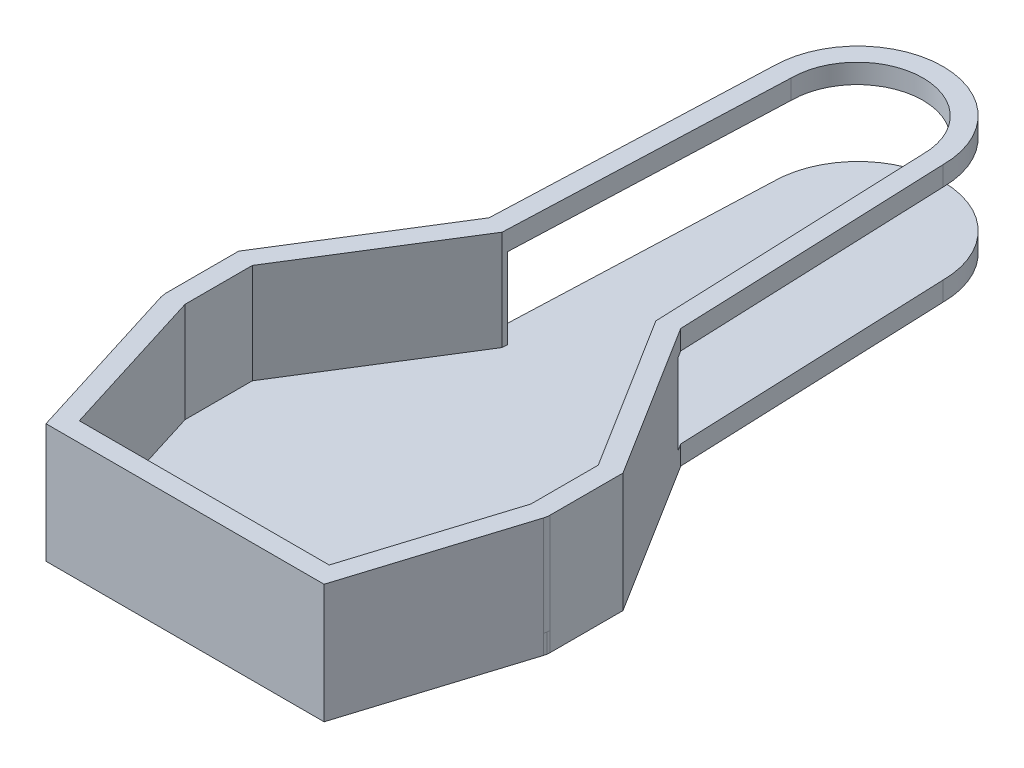
SolidWorks part; units mm, degrees
ref_plane "Front Plane" through (0, 0, 0) normal (0, 0, 1) x (1, 0, 0)
ref_plane "Top Plane" through (0, 0, 0) normal (0, 1, 0) x (1, 0, 0)
ref_plane "Right Plane" through (0, 0, 0) normal (1, 0, 0) x (0, 0, -1)
sketch "Sketch1" plane through (0, 0, 0) normal (0, 1, 0) x (1, 0, 0)
  line L0 (0, 0) -> (82.55, 0)
  line L1 (82.55, 0) -> (98.4289, 50.8)
  line L2 (0, 0) -> (-15.8711, 50.8)
  line L3 (98.4289, 50.8) -> (98.4289, 73.025)
  line L4 (-15.8711, 50.8) -> (-15.8711, 73.025)
  line L5 (-15.8711, 73.025) -> (15.8789, 123.825)
  line L6 (98.4289, 73.025) -> (66.6789, 123.825)
  line L7 (-15.8711, 50.8) -> (98.4289, 50.8)
  line L8 (15.8789, 123.825) -> (19.5001, 215.7158)
  line L9 (63.0578, 215.7158) -> (66.6789, 123.825)
  line L10 (-22.2211, 50.8) -> (-22.2211, 74.8462)
  line L11 (-22.2211, 74.8462) -> (9.6003, 125.7603)
  line L12 (9.6003, 125.7603) -> (13.155, 215.9659)
  line L13 (69.4029, 215.9659) -> (72.9576, 125.7603)
  line L14 (104.7789, 74.8462) -> (72.9576, 125.7603)
  line L15 (104.7789, 50.8) -> (104.7789, 74.8462)
  line L16 (87.2181, -6.35) -> (104.4897, 48.9055)
  line L17 (-4.6688, -6.35) -> (87.2181, -6.35)
  line L18 (-4.6688, -6.35) -> (-21.9322, 48.9064)
  line L19 (-21.9322, 48.9064) -> (-22.2211, 50.8)
  circle A0 centre (41.2789, 215.7158) radius 21.7789
  arc A2 (104.4897, 48.9055) -> (104.7789, 50.8) centre (98.4289, 50.8) ccw
  arc A3 (13.155, 215.9659) -> (69.4029, 215.9659) centre (41.2789, 215.9659) cw
  dimension "D1" = 22.225
  dimension "D2" = 114.3
  dimension "D3" = 107.35
  dimension "D4" = 107.358
  dimension "D5" = 82.55
  dimension "D6" = 50.8
  dimension "D7" = 22.225
  dimension "D8" = 31.75
  dimension "D9" = 31.75
  dimension "D10" = 50.8
  dimension "D11" = 50.8
  dimension "D12" = 25.4
  dimension "D13" = 6.35
extrude "Boss-Extrude1" add sketch "Sketch1" along normal blind 33.02 contours A3 L12 L11 L10 L19 L18 L17 L16 A2 L15 L14 L13 A0 L9 L6 L3 L1 L0 L2 L4 L5 L8 region at (-19.4131, 0, -62.8231)
sketch "Sketch2" plane through (0, 0, 0) normal (0, -1, 0) x (1, 0, 0)
  line L0 (-4.6688, 6.35) -> (87.2181, 6.35)
  line L1 (87.2181, 6.35) -> (104.4897, -48.9055)
  line L2 (104.4897, -48.9055) -> (104.7062, -49.8418)
  line L3 (104.7062, -49.8418) -> (104.7789, -50.8)
  line L4 (104.7789, -50.8) -> (104.7789, -74.8462)
  line L5 (104.7789, -74.8462) -> (72.9576, -125.7603)
  line L6 (72.9576, -125.7603) -> (69.4029, -215.9659)
  line L7 (13.155, -215.9659) -> (9.6003, -125.7603)
  line L8 (9.6003, -125.7603) -> (-22.2211, -74.8462)
  line L9 (-22.2211, -74.8462) -> (-22.2211, -50.8)
  line L10 (-22.2211, -50.8) -> (-21.9322, -48.9064)
  line L11 (-21.9322, -48.9064) -> (-4.6688, 6.35)
  line L12 (-4.6688, 6.35) -> (87.2181, 6.35)
  line L13 (0, 0) -> (82.55, 0)
  line L14 (82.55, 0) -> (98.4289, -50.8)
  line L15 (98.4289, -50.8) -> (98.4289, -73.025)
  line L16 (98.4289, -73.025) -> (66.6789, -123.825)
  line L17 (66.6789, -123.825) -> (63.0578, -215.7158)
  line L18 (19.5001, -215.7158) -> (15.8789, -123.825)
  line L19 (15.8789, -123.825) -> (-15.8711, -73.025)
  line L20 (-15.8711, -73.025) -> (-15.8711, -50.8)
  line L21 (-15.8711, -50.8) -> (0, 0)
  line L22 (0, 0) -> (82.55, 0)
  line L23 (82.55, 0) -> (98.4289, -50.8)
  arc A0 (104.7789, -50.8) -> (104.4897, -48.9055) centre (98.4289, -50.8) ccw construction
  arc A1 (19.5001, -215.7158) -> (63.0578, -215.7158) centre (41.2789, -215.7158) ccw
  arc A2 (13.155, -215.9659) -> (69.4029, -215.9659) centre (41.2789, -215.9659) ccw
  arc M1 (13.155, -215.9659) -> (69.4029, -215.9659) centre (41.2789, -215.9659) ccw
  line M2 (69.4029, -215.9659) -> (72.9576, -125.7603)
  line M3 (72.9576, -125.7603) -> (104.7789, -74.8462)
  line M4 (104.7789, -74.8462) -> (104.7789, -50.8)
  line M6 (104.4897, -48.9055) -> (87.2181, 6.35)
  line M7 (87.2181, 6.35) -> (-4.6688, 6.35)
  line M8 (-4.6688, 6.35) -> (-21.9322, -48.9064)
  line M9 (-21.9322, -48.9064) -> (-22.2211, -50.8)
  line M10 (-22.2211, -50.8) -> (-22.2211, -74.8462)
  line M11 (-22.2211, -74.8462) -> (9.6003, -125.7603)
  line M12 (9.6003, -125.7603) -> (13.155, -215.9659)
  arc M13 (63.0578, -215.7158) -> (19.5001, -215.7158) centre (41.2789, -215.7158) cw
  line M14 (19.5001, -215.7158) -> (15.8789, -123.825)
  line M15 (15.8789, -123.825) -> (-15.8711, -73.025)
  line M16 (-15.8711, -73.025) -> (-15.8711, -50.8)
  line M17 (-15.8711, -50.8) -> (0, 0)
  line M18 (0, 0) -> (82.55, 0)
  line M19 (82.55, 0) -> (98.4289, -50.8)
  line M20 (98.4289, -50.8) -> (98.4289, -73.025)
  line M21 (98.4289, -73.025) -> (66.6789, -123.825)
  line M22 (66.6789, -123.825) -> (63.0578, -215.7158)
extrude "Boss-Extrude2" add sketch "Sketch2" along normal blind 6.35 contours L3 L2 M6 M7 M8 M9 M10 M11 M12 M1 M2 M3 M4 M22 M13 M14 M15 M16 M17 M18 M19 M20 M21 | M13 M22 M21 M20 M19 M18 M17 M16 M15 M14 region at (41.2747, 0, 3.542) region at (41.2784, 0, -94.4865)
sketch "Sketch3" plane through (4.6372, 0, 0.1827) normal (-0.9992, 0, -0.0394) x (-0.0394, 0, 0.9992)
  line L0 (-216.3164, -6.35) -> (-216.3164, 0)
  line L1 (-216.3164, 33.02) -> (-216.3164, -6.35) construction
  line L2 (-216.3164, 0) -> (-126.0408, 0)
  line L3 (-126.0408, 33.02) -> (-126.0408, -6.35) construction
  line L4 (-216.3164, 33.02) -> (-216.3164, 26.5967)
  line L5 (-216.3164, 26.5967) -> (-126.0408, 26.5967)
  line L6 (-126.0408, 26.5967) -> (-126.0408, 0)
  line L7 (-216.3164, 0) -> (-264.6903, 0)
  line L8 (-264.6903, 0) -> (-264.6903, 26.5967)
  line L9 (-264.6903, 26.5967) -> (-216.3164, 26.5967)
  line M1 (-216.3164, 33.02) -> (-216.3164, -6.35)
  line M3 (-126.0408, -6.35) -> (-126.0408, 33.02)
extrude "Cut-Extrude1" cut sketch "Sketch3" against normal blind 96.52 and the other way blind 96.52 contours L5 L2 M1 M3 | L9 L8 L7 M1 region at (11.3776, 13.2983, -170.8631) region at (14.1074, 13.2983, -240.134)
